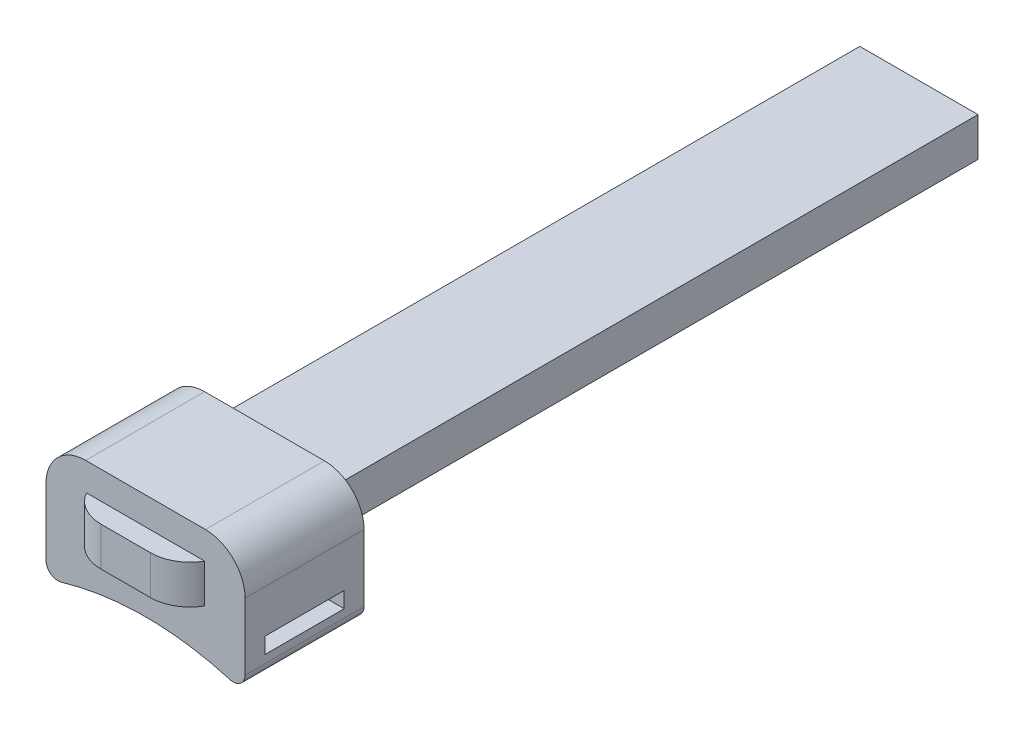
SolidWorks part; units mm, degrees
ref_plane "Front Plane" through (0, 0, 0) normal (0, 0, 1) x (1, 0, 0)
ref_plane "Top Plane" through (0, 0, 0) normal (0, 1, 0) x (1, 0, 0)
ref_plane "Right Plane" through (0, 0, 0) normal (1, 0, 0) x (0, 0, -1)
sketch "Sketch1" plane through (0, 0, 0) normal (0, 0, 1) x (1, 0, 0)
  line L0 (0, 0) -> (14.9, 0)
  line L1 (0, 0) -> (-14.9, 0)
  line L2 (-14.9, 0) -> (-14.9, 9.8)
  line L3 (-14.9, 9.8) -> (14.9, 9.8)
  line L4 (14.9, 9.8) -> (14.9, 0)
extrude "Boss-Extrude1" add sketch "Sketch1" against normal blind 200
ref_plane "Plane1" through (0, 0, -5) normal (0, 0, 1) x (1, 0, 0)
sketch "Sketch2" plane through (0, 0, -5) normal (0, 0, 1) x (1, 0, 0)
  line L0 (-14.9, 9.8) -> (-14.9, 0)
  line L1 (-14.9, 0) -> (14.9, 0)
  line L2 (-21.6618, -13) -> (-22.1, -13)
  line L4 (21.6618, -13) -> (22.1, -13)
  line L5 (14.9, 0) -> (14.9, 9.8)
  line L6 (-14.9, 16.8) -> (-15.1, 16.8)
  line L7 (-25.1, 6.8) -> (-25.1, -10)
  line L8 (-14.9, 16.8) -> (15.1, 16.8)
  line L9 (25.1, 6.8) -> (25.1, -10)
  line L10 (14.9, 9.8) -> (-14.9, 9.8)
  arc A0 (-25.1, -10) -> (-21.25, -12.8771) centre (-22.1, -10) ccw
  arc A1 (21.25, -12.8771) -> (25.1, -10) centre (22.1, -10) ccw
  arc A2 (-15.1, 16.8) -> (-25.1, 6.8) centre (-15.1, 6.8) ccw
  arc A3 (25.1, 6.8) -> (15.1, 16.8) centre (15.1, 6.8) ccw
  arc A4 (21.6618, -13) -> (-21.6618, -13) centre (0, -84.8037) ccw
  dimension "D1" = 150
extrude "Boss-Extrude2" add sketch "Sketch2" against normal blind 30 contours A4 A1 L9 A3 L8 L6 A2 L7 A0 L10 L5 L1 L0 region at (-23.8085, -11.7085, -5)
fillet "Fillet1" radius 10 1 edges at (14.9, 4.9, 0)
fillet "Fillet2" radius 10 1 edges at (-14.9, 4.9, 0)
sketch "Sketch3" plane through (25.1, 0, 0) normal (1, 0, 0) x (0, 0, -1)
  line L0 (20, -10) -> (20, -8)
  line L1 (35, -10) -> (5, -10) construction
  line L2 (20, -8) -> (10, -8)
  line L3 (20, -8) -> (30, -8)
  line L4 (10, -8) -> (10, -4)
  line L5 (10, -4) -> (30, -4)
  line L6 (30, -4) -> (30, -8)
extrude "Cut-Extrude1" cut sketch "Sketch3" against normal blind 56 contours L6 L5 L4 L2 L3 region at (25.1, -6, -20)
